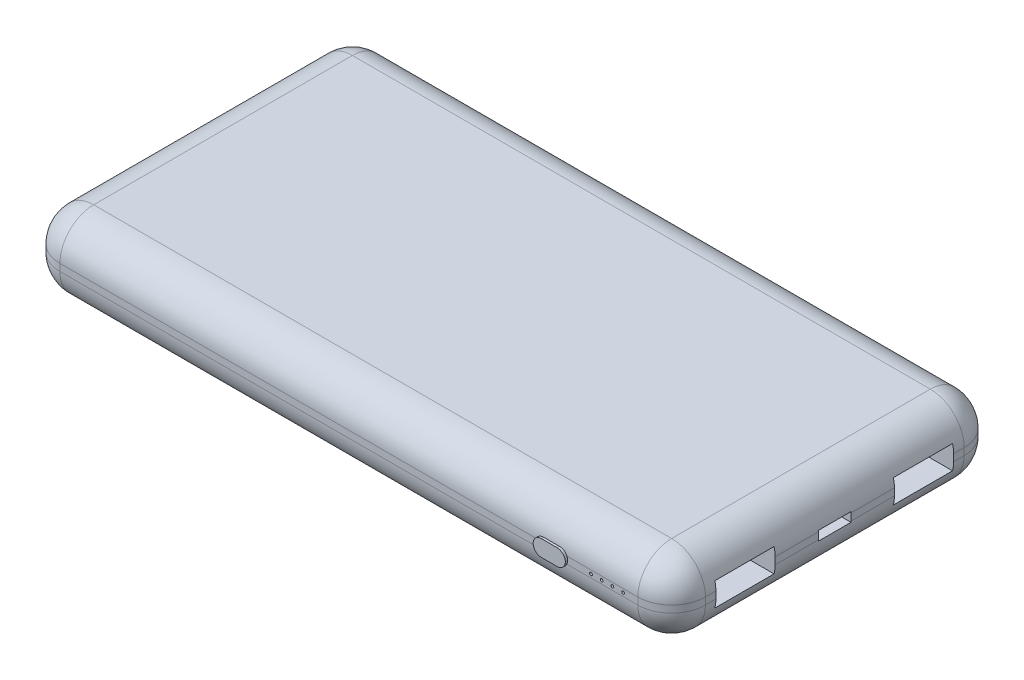
SolidWorks part; units mm, degrees
ref_plane "Front Plane" through (0, 0, 0) normal (0, 0, 1) x (1, 0, 0)
ref_plane "Top Plane" through (0, 0, 0) normal (0, 1, 0) x (1, 0, 0)
ref_plane "Right Plane" through (0, 0, 0) normal (1, 0, 0) x (0, 0, -1)
ref_axis "X Axis" through (-84.3881, 0, 0) along (1, 0, 0)
ref_axis "Y Axis" through (0, 58.113, 0) along (0, -1, 0)
ref_axis "Z Axis" through (0, 0, -88.99) along (0, 0, 1)
sketch "Sketch1" plane through (0, 0, 0) normal (0, 1, 0) x (1, 0, 0)
  line L1 (-69.25, -35) -> (69.25, -35)
  line L2 (-69.25, -35) -> (-69.25, 35)
  line L3 (-69.25, 35) -> (69.25, 35)
  line L4 (69.25, -35) -> (69.25, 35)
  line L5 (-69.25, -35) -> (69.25, 35) construction
  line L6 (-69.25, 35) -> (69.25, -35) construction
  point P0 (0, 0)
  dimension "D1" = 138.5
  dimension "D2" = 70
extrude "Boss-Extrude1" add sketch "Sketch1" along normal mid plane 16
fillet "Fillet1" radius 7.25 12 edges at (-69.25, 0, -35) (69.25, 0, -35) (-69.25, 0, 35) (69.25, 0, 35) (0, -8, -35) (-69.25, -8, 0) (0, -8, 35) (69.25, -8, 0) (0, 8, 35) (-69.25, 8, 0) (0, 8, -35) (69.25, 8, 0)
sketch "Sketch3" plane through (69.25, 0, 0) normal (1, 0, 0) x (0, 0, -1)
  line L0 (-35, -0.75) -> (-35, 0.75) construction
  line L1 (-25.5, -2.54) -> (-12.8, -2.54)
  line L2 (-25.5, -2.54) -> (-25.5, 2.54)
  line L3 (-25.5, 2.54) -> (-12.8, 2.54)
  line L4 (-12.8, -2.54) -> (-12.8, 2.54)
  line L5 (-25.5, -2.54) -> (-12.8, 2.54) construction
  line L6 (-25.5, 2.54) -> (-12.8, -2.54) construction
  line L7 (0, 8.8) -> (0, -8.8) construction
  line L8 (25.5, 2.54) -> (12.8, -2.54) construction
  line L9 (25.5, -2.54) -> (12.8, 2.54) construction
  line L10 (12.8, -2.54) -> (12.8, 2.54)
  line L11 (25.5, 2.54) -> (12.8, 2.54)
  line L12 (25.5, -2.54) -> (25.5, 2.54)
  line L13 (25.5, -2.54) -> (12.8, -2.54)
  point P0 (-19.15, 0)
  point P15 (19.15, 0)
  dimension "D1" = 12.7
  dimension "D2" = 5.08
  dimension "D3" = 9.5
extrude "USB-A" cut sketch "Sketch3" against normal blind 11.25
sketch "Sketch4" plane through (69.25, 0, 0) normal (1, 0, 0) x (0, 0, -1)
  line L1 (-3.5, -1) -> (3.5, -1)
  line L2 (-3.5, -1) -> (-3.5, 1)
  line L3 (-3.5, 1) -> (3.5, 1)
  line L4 (3.5, -1) -> (3.5, 1)
  line L5 (-3.5, -1) -> (3.5, 1) construction
  line L6 (-3.5, 1) -> (3.5, -1) construction
  point P0 (0, 0)
  dimension "D1" = 2
  dimension "D2" = 7
extrude "USB-micro-NOTtoSCALE" cut sketch "Sketch4" against normal blind 5
sketch "Sketch5" plane through (0, 0, -35) normal (0, 0, -1) x (-1, 0, 0)
  line L0 (-69.25, -0.75) -> (-69.25, 0.75) construction
  line L1 (-50.2, -1.27) -> (-41.818, -1.27)
  line L2 (-50.2, -1.27) -> (-50.2, 1.27)
  line L3 (-50.2, 1.27) -> (-41.818, 1.27)
  line L4 (-41.818, -1.27) -> (-41.818, 1.27)
  line L5 (-50.2, -1.27) -> (-41.818, 1.27) construction
  line L6 (-50.2, 1.27) -> (-41.818, -1.27) construction
  point P0 (-46.009, 0)
  dimension "D1" = 19.05
  dimension "D2" = 2.54
  dimension "D3" = 8.382
extrude "USB-C" cut sketch "Sketch5" against normal blind 8
fillet "Fillet2" radius 1.27 4 edges at (41.818, 1.27, -30.9907) (41.818, -1.27, -30.9907) (50.2, -1.27, -30.9907) (50.2, 1.27, -30.9907)
sketch "Sketch6" plane through (0, 0, 35) normal (0, 0, 1) x (1, 0, 0)
  line L0 (69.25, 0.75) -> (69.25, -0.75) construction
  line L1 (40.04, -1.75) -> (46.94, -1.75)
  line L2 (40.04, -1.75) -> (40.04, 1.75)
  line L3 (40.04, 1.75) -> (46.94, 1.75)
  line L4 (46.94, -1.75) -> (46.94, 1.75)
  line L5 (40.04, -1.75) -> (46.94, 1.75) construction
  line L6 (40.04, 1.75) -> (46.94, -1.75) construction
  point P0 (43.49, 0)
  dimension "D1" = 29.21
  dimension "D2" = 6.9
  dimension "D3" = 3.5
extrude "battery level" add sketch "Sketch6" along normal blind 0.5
fillet "Fillet3" radius 1.75 4 edges at (40.04, -1.75, 35.25) (40.04, 1.75, 35.25) (46.94, -1.75, 35.25) (46.94, 1.75, 35.25)
sketch "Sketch7" plane through (0, 0, 35) normal (0, 0, 1) x (1, 0, 0)
  line L0 (51.94, 0.75) -> (51.94, -0.75) construction
  line L1 (62, 0.75) -> (46.7711, 0.75) construction
  line L2 (46.7711, -0.75) -> (62, -0.75) construction
  line L3 (51.94, 0) -> (62, 0) construction
  line L4 (62, -0.75) -> (62, 0.75) construction
  circle A0 centre (51.94, 0) radius 0.3
  circle A1 centre (54.24, 0) radius 0.3
  circle A2 centre (56.54, 0) radius 0.3
  circle A3 centre (58.84, 0) radius 0.3
  dimension "D2" = 0.6
  dimension "D1" = 5
  dimension "D3" = 4
extrude "battery lights" cut sketch "Sketch7" against normal blind 1
